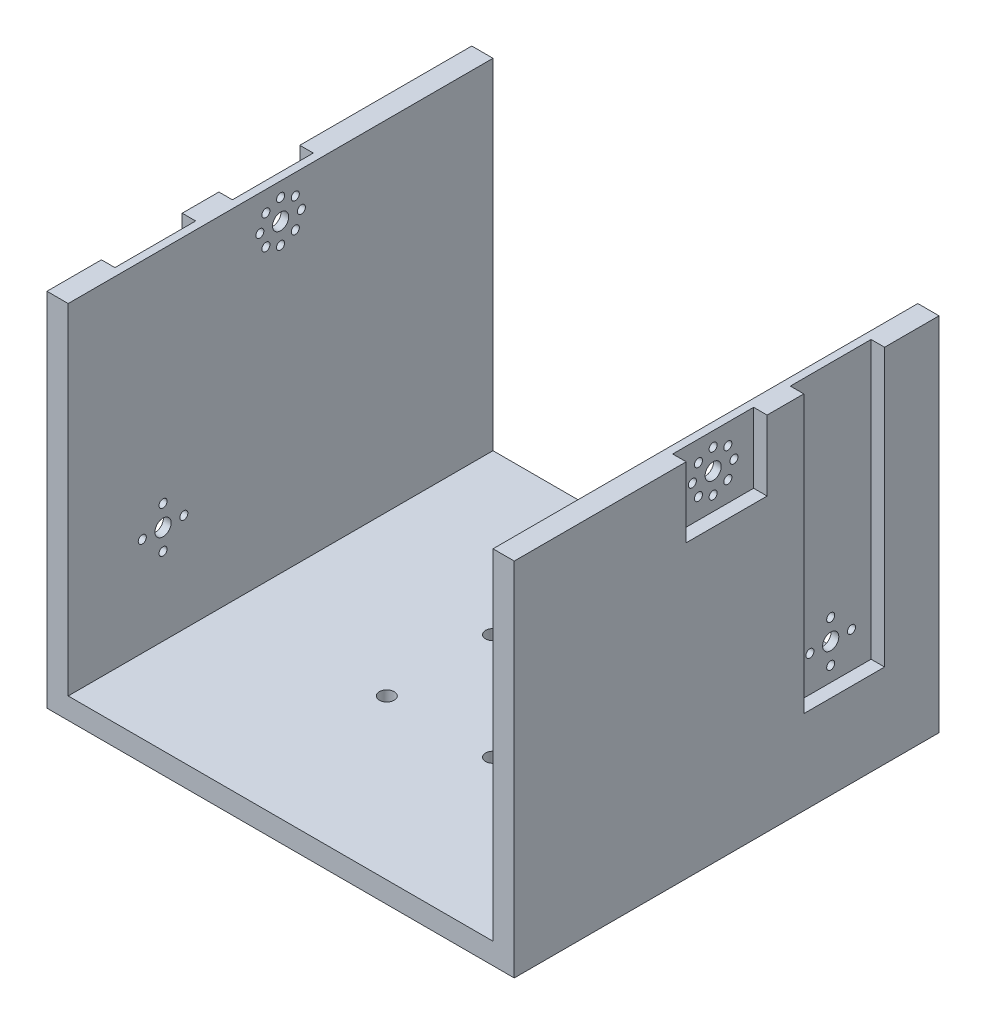
SolidWorks part; units mm, degrees
ref_plane "Front" through (0, 0, 0) normal (0, 0, 1) x (1, 0, 0)
ref_plane "Top" through (0, 0, 0) normal (0, 1, 0) x (1, 0, 0)
ref_plane "Right" through (0, 0, 0) normal (1, 0, 0) x (0, 0, -1)
sketch "Sketch2" plane through (0, 0, 0) normal (0, 1, 0) x (1, 0, 0)
  line L0 (0, 0) -> (0, -100) construction
  line L1 (-100, -100) -> (100, -100)
  line L2 (-100, -100) -> (-100, 100)
  line L3 (-100, 100) -> (100, 100)
  line L4 (100, -100) -> (100, 100)
  line L5 (0, 0) -> (-100, 0) construction
  point P0 (0, 0)
  dimension "D1" = 200
  dimension "D2" = 200
extrude "Boss-Extrude1" add sketch "Sketch2" along normal blind 10
sketch "Sketch3" plane through (0, 0, 0) normal (0, 1, 0) x (1, 0, 0)
  line L0 (-100, -100) -> (100, -100) construction
  line L1 (-100, 100) -> (-110, 100)
  line L2 (-100, 100) -> (-100, -100)
  line L3 (-100, -100) -> (-110, -100)
  line L4 (-110, 100) -> (-110, -100)
  line L5 (0, 0) -> (0, 100) construction
  line L6 (100, 100) -> (-100, 100) construction
  line L7 (110, 100) -> (110, -100)
  line L8 (100, -100) -> (110, -100)
  line L9 (100, 100) -> (100, -100)
  line L10 (100, 100) -> (110, 100)
  dimension "D1" = 10
extrude "Boss-Extrude2" add sketch "Sketch3" along normal blind 170
sketch "Sketch4" plane through (0, 10, 0) normal (0, 1, 0) x (1, 0, 0)
  point P4 (0, 0)
hole_wizard "M6 Clearance Hole1" positions "Sketch5" profile "Sketch6" hole size "M6" standard "ANSI Metric" end condition up to next
sketch "Sketch5" plane through (0, 10, 0) normal (0, 1, 0) x (1, 0, 0)
  line L0 (0, 0) -> (0, 25) construction
  line L1 (0, 25) -> (-25, 25) construction
  line L3 (0, 25) -> (25, 25) construction
  point P0 (-25, 25)
  point P13 (25, 25)
  point P14 (25, -25)
  point P15 (-25, -25)
  dimension "D1" = 25
  dimension "D2" = 4
sketch "Sketch6" plane through (-25, 10, -25) normal (1, 0, 0) x (0, 0, 1)
  line L0 (0, 0) -> (0, 10)
  line L1 (0, 10) -> (3.5, 10)
  line L2 (3.5, 10) -> (3.5, 0)
  line L5 (3.5, 0) -> (0, 0)
  line L11 (0, -6.35) -> (0, 107.95) construction
  dimension "Thru Hole Dia." = 7
  dimension "Thru Hole Depth" = 10
sketch "Sketch7" plane through (100, 0, 0) normal (-1, 0, 0) x (0, 0, 1)
  line L0 (-100, 170) -> (100, 170) construction
  line L1 (0, 153.49) -> (0, 163.269) construction
  line L2 (0, 153.49) -> (0, 163.269) construction
  circle A0 centre (0, 153.49) radius 3.81
  circle A1 centre (0, 163.269) radius 1.8987
  circle A2 centre (6.9148, 160.4048) radius 1.8987
  circle A3 centre (9.779, 153.49) radius 1.8987
  circle A4 centre (6.9148, 146.5752) radius 1.8987
  circle A5 centre (0, 143.711) radius 1.8987
  circle A6 centre (-6.9148, 146.5752) radius 1.8987
  circle A7 centre (-9.779, 153.49) radius 1.8987
  circle A8 centre (-6.9148, 160.4048) radius 1.8987
  point P7 (0, 170)
  dimension "D1" = 7.62
  dimension "D3" = 3.7973
  dimension "D2" = 16.51
  dimension "D6" = 9.779
  dimension "D5" = 8
extrude "Cut-Extrude1" cut sketch "Sketch7" against normal through all both and the other way through all
sketch "Sketch8" plane through (0, 170, 0) normal (0, 1, 0) x (1, 0, 0)
  line L1 (103.65, -19.05) -> (110, -19.05)
  line L2 (103.65, -19.05) -> (103.65, 19.05)
  line L3 (103.65, 19.05) -> (110, 19.05)
  line L4 (110, -19.05) -> (110, 19.05)
  line L5 (103.65, -19.05) -> (110, 19.05) construction
  line L6 (103.65, 19.05) -> (110, -19.05) construction
  line L9 (110, -100) -> (110, 100) construction
  line L10 (0, 0) -> (0, 100) construction
  line L11 (100, 100) -> (-100, 100) construction
  line L13 (-103.65, 19.05) -> (-110, -19.05) construction
  line L14 (-103.65, -19.05) -> (-110, 19.05) construction
  line L16 (-110, -19.05) -> (-110, 19.05)
  line L17 (-103.65, 19.05) -> (-110, 19.05)
  line L18 (-103.65, -19.05) -> (-103.65, 19.05)
  line L19 (-103.65, -19.05) -> (-110, -19.05)
  point P0 (106.825, 0)
  point P12 (110, 0)
  point P23 (-106.825, 0)
  dimension "D1" = 38.1
  dimension "D2" = 6.35
extrude "Cut-Extrude2" cut sketch "Sketch8" against normal blind 33.02
sketch "Sketch9" plane through (110, 0, 0) normal (1, 0, 0) x (0, 0, -1)
  line L0 (38.8318, 39.6302) -> (44.9278, 39.6302) construction
  line L2 (74.3518, 73.1682) -> (74.3518, 39.6202)
  line L3 (74.3518, 39.6202) -> (36.3318, 39.6202)
  line L4 (36.3318, 73.1682) -> (36.3318, 39.6202)
  line L5 (74.3518, 73.1682) -> (36.3318, 39.6202) construction
  line L6 (74.3518, 39.6202) -> (36.3318, 73.1682) construction
  line L7 (38.8318, 48.7742) -> (38.8318, 39.6302) construction
  line L13 (74.3518, 73.1682) -> (74.3518, 170)
  line L14 (19.05, 170) -> (100, 170) construction
  line L15 (74.3518, 170) -> (36.3318, 170)
  line L16 (36.3318, 170) -> (36.3318, 73.1682)
  point P0 (55.3418, 56.3942)
  point P10 (55.3418, 66.1732)
  point P11 (45.5628, 56.3942)
  point P13 (55.3418, 46.6152)
  point P15 (65.1208, 56.3942)
  dimension "D1" = 0.01
  dimension "D2" = 2.5
extrude "Cut-Extrude3" cut sketch "Sketch9" against normal blind 6.35
sketch "Sketch11" plane through (103.65, 0, 0) normal (1, 0, 0) x (0, 0, -1)
  circle A0 centre (55.3418, 56.3942) radius 3.81
  circle A1 centre (0, 153.49) radius 3.81 construction
extrude "Cut-Extrude4" cut sketch "Sketch11" against normal up to next
hole_wizard "#6 Clearance Hole1" positions "Sketch12" profile "Sketch13" hole size "#6" standard "ANSI Inch" end condition up to next
sketch "Sketch12" plane through (103.65, 0, 0) normal (1, 0, 0) x (0, 0, -1)
  point P0 (55.3418, 66.1732)
  point P3 (45.5628, 56.3942)
  point P6 (65.1208, 56.3942)
  point P10 (55.3418, 46.6152)
sketch "Sketch13" plane through (103.65, 66.1732, -55.3418) normal (0, 1, 0) x (0, 0, -1)
  line L0 (0, 0) -> (0, 3.65)
  line L1 (0, 3.65) -> (1.8986, 3.65)
  line L2 (1.8986, 3.65) -> (1.8986, 0)
  line L5 (1.8986, 0) -> (0, 0)
  line L11 (0, -6.35) -> (0, 107.95) construction
  dimension "Thru Hole Dia." = 3.7973
  dimension "Thru Hole Depth" = 3.65
ref_plane "Plane1" through (0, 0, 0) normal (-0.7071, 0, 0.7071) x (0.7071, 0, 0.7071)
ref_axis "Axis1" through (0, 0, 0) along (0, 1, 0)
pattern_circular "CirPattern1" count 2 over 360 about axis through (0, 0, 0) along (0, 1, 0) of "Cut-Extrude3", "Cut-Extrude4", "#6 Clearance Hole1"
equation "\"Longueur\"= 200"
equation "\"D2@Sketch2\"=\"Longueur\""
equation "\"Largeur\"=200"
equation "\"D1@Sketch2\"=\"Largeur\""
